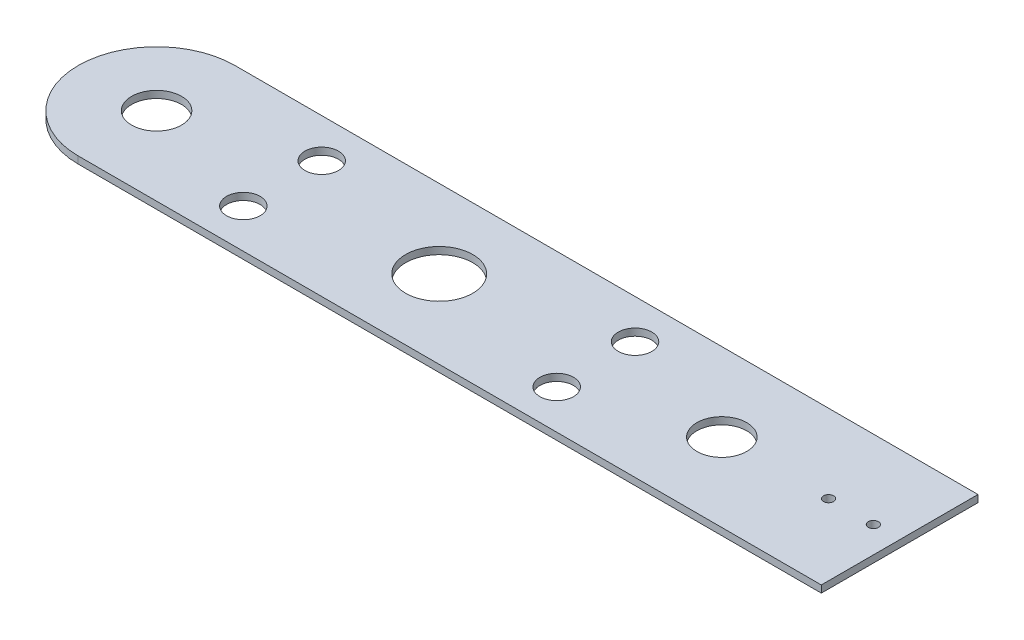
SolidWorks part; units mm, degrees
ref_plane "Front Plane" through (0, 0, 0) normal (0, 0, 1) x (1, 0, 0)
ref_plane "Top Plane" through (0, 0, 0) normal (0, 1, 0) x (1, 0, 0)
ref_plane "Right Plane" through (0, 0, 0) normal (1, 0, 0) x (0, 0, -1)
sketch "Sketch1" plane through (0, 0, 0) normal (0, 1, 0) x (1, 0, 0)
  line L0 (126.2582, 0) -> (-126.2582, 0)
  line L1 (-126.2582, 35) -> (126.2582, 35)
  line L3 (-126.2582, -35) -> (126.2582, -35)
  line L4 (-70, 35) -> (-70, 0) construction
  line L5 (-70, 0) -> (-70, -35) construction
  line L6 (70, 35) -> (70, 0) construction
  line L7 (70, 0) -> (70, -35) construction
  line L8 (161.2582, 35) -> (161.2582, -35) construction
  line L9 (161.2582, 35) -> (126.2582, 35)
  line L10 (161.2582, -35) -> (126.2582, -35)
  line L11 (161.2582, 35) -> (205.7082, 35)
  line L12 (205.7082, 35) -> (205.7082, -35)
  line L13 (205.7082, -35) -> (161.2582, -35)
  line L14 (205.7082, 0) -> (161.2582, 0) construction
  circle A0 centre (-126.2582, 0) radius 35
  circle A2 centre (-126.2582, 0) radius 11.15
  circle A3 centre (126.2582, 0) radius 11.15
  circle A4 centre (0, 0) radius 15
  circle A5 centre (-70, -17.5) radius 7.5
  circle A6 centre (-70, 17.5) radius 7.5
  circle A7 centre (70, 17.5) radius 7.5
  circle A8 centre (70, -17.5) radius 7.5
  circle A9 centre (173.9582, 0) radius 2.25
  circle A10 centre (193.9582, 0) radius 2.25
  point P4 (0, 0)
  point P31 (-161.2582, 0)
  point P32 (161.2582, 0)
  dimension "D1" = 22.3
  dimension "D2" = 30
  dimension "D3" = 70
  dimension "D4" = 15
  dimension "D10" = 4.5
  dimension "D5" = 70
  dimension "D6" = 70
  dimension "D7" = 322.5164
  dimension "D8" = 44.45
  dimension "D9" = 20
  dimension "D11" = 12.7
extrude "Boss-Extrude1" add sketch "Sketch1" along normal blind 3.175 contours A4 A3 A0 L3 L10 L13 L12 L11 L9 L1 A8 A7 A6 A5 | A2 A0 region at (-102.2095, 0, 24.0487) region at (-99.1105, 0, -27.1477)
